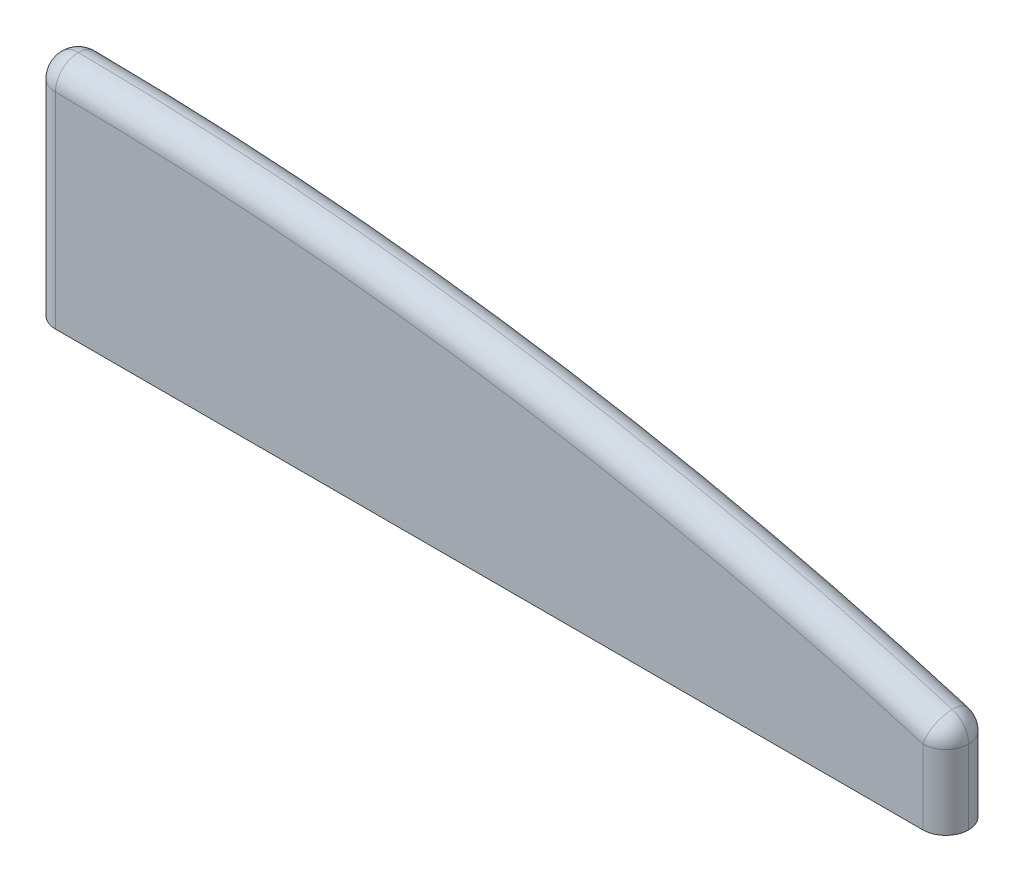
SolidWorks part; units mm, degrees
ref_plane "Piano frontale" through (0, 0, 0) normal (0, 0, 1) x (1, 0, 0)
ref_plane "Piano superiore" through (0, 0, 0) normal (0, 1, 0) x (1, 0, 0)
ref_plane "Piano destro" through (0, 0, 0) normal (1, 0, 0) x (0, 0, -1)
sketch "Schizzo1" plane through (0, 0, 0) normal (0, 0, 1) x (1, 0, 0)
  line L1 (0, 0) -> (20, 0)
  line L2 (0, 0) -> (0, 5)
  line L4 (20, 0) -> (20, 2)
  arc A0 (0, 5) -> (20, 2) centre (0, -63.1667) cw
  dimension "D4" = 68.1667
  dimension "D1" = 20
  dimension "D2" = 5
  dimension "D3" = 2
extrude "Estrusione-Estrusione1" add sketch "Schizzo1" along normal blind 1
fillet "Raccordo1" radius 0.5 6 edges at (0, 2.5, 1) (0, 2.5, 0) (20, 1, 0) (20, 1, 1) (10.1119, 4.2458, 1) (10.1119, 4.2458, 0)
